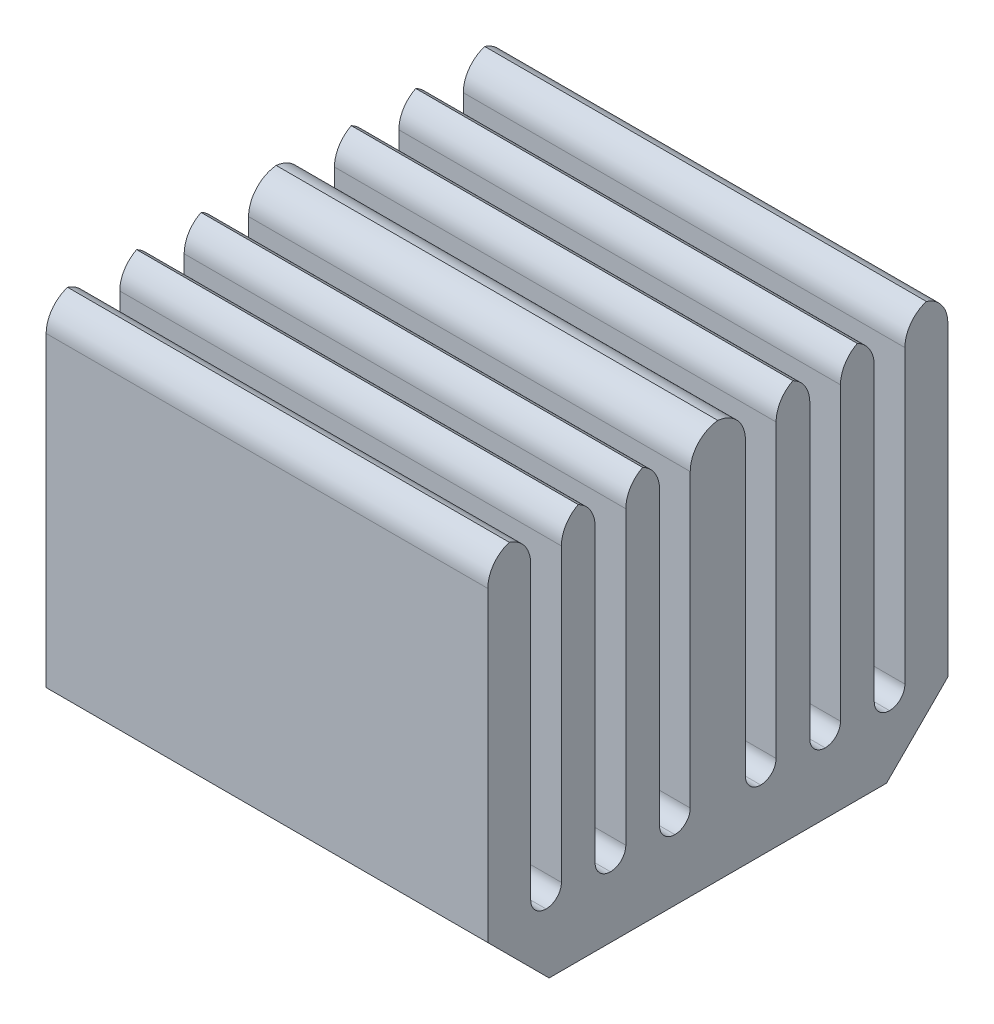
SolidWorks part; units mm, degrees
material "2.0060 (Cu-ETP)"
ref_plane "Ebene vorne" through (0, 0, 0) normal (0, 0, 1) x (1, 0, 0)
ref_plane "Ebene oben" through (0, 0, 0) normal (0, 1, 0) x (1, 0, 0)
ref_plane "Ebene rechts" through (0, 0, 0) normal (1, 0, 0) x (0, 0, -1)
sketch "Skizze1" plane through (0, 0, 0) normal (0, 1, 0) x (1, 0, 0)
  line L1 (-7.2, -7.5) -> (7.2, -7.5)
  line L2 (-7.2, -7.5) -> (-7.2, 7.5)
  line L3 (-7.2, 7.5) -> (7.2, 7.5)
  line L4 (7.2, -7.5) -> (7.2, 7.5)
  line L5 (-7.2, -7.5) -> (7.2, 7.5) construction
  line L6 (-7.2, 7.5) -> (7.2, -7.5) construction
  point P0 (0, 0)
  dimension "D1" = 14.4
  dimension "D2" = 15
extrude "Aufsatz-Linear austragen1" add sketch "Skizze1" along normal blind 13
sketch "Skizze2" plane through (0, 13, 0) normal (0, 1, 0) x (1, 0, 0)
  line L0 (-7.2, 7.5) -> (-7.2, -7.5) construction
  line L1 (-7.2, -6.1) -> (7.2, -6.1)
  line L2 (-7.2, -6.1) -> (-7.2, -5.1)
  line L3 (-7.2, -5.1) -> (7.2, -5.1)
  line L4 (7.2, -6.1) -> (7.2, -5.1)
  line L5 (7.2, -7.5) -> (7.2, 7.5) construction
  line L6 (7.2, 7.5) -> (-7.2, 7.5) construction
  line L7 (-7.2, -3) -> (7.2, -3)
  line L8 (-7.2, -3) -> (-7.2, -4)
  line L9 (-7.2, -4) -> (7.2, -4)
  line L10 (7.2, -3) -> (7.2, -4)
  line L11 (-7.2, -0.9) -> (7.2, -0.9)
  line L12 (-7.2, -0.9) -> (-7.2, -1.9)
  line L13 (-7.2, -1.9) -> (7.2, -1.9)
  line L14 (7.2, -0.9) -> (7.2, -1.9)
  line L15 (-7.2, 1.9) -> (7.2, 1.9)
  line L16 (-7.2, 1.9) -> (-7.2, 0.9)
  line L17 (-7.2, 0.9) -> (7.2, 0.9)
  line L18 (7.2, 1.9) -> (7.2, 0.9)
  line L19 (-7.2, 4) -> (7.2, 4)
  line L20 (-7.2, 4) -> (-7.2, 3)
  line L21 (-7.2, 3) -> (7.2, 3)
  line L22 (7.2, 4) -> (7.2, 3)
  line L23 (-7.2, 6.1) -> (7.2, 6.1)
  line L24 (-7.2, 6.1) -> (-7.2, 5.1)
  line L25 (-7.2, 5.1) -> (7.2, 5.1)
  line L26 (7.2, 6.1) -> (7.2, 5.1)
  line L27 (-7.2, -7.5) -> (7.2, -7.5) construction
  dimension "D1" = 1
  dimension "D2" = 1.4
  dimension "D3" = 1.1
  dimension "D4" = 1.1
  dimension "D5" = 1.1
  dimension "D6" = 1.1
  dimension "D7" = 1.4
extrude "Schnitt-Linear austragen1" cut sketch "Skizze2" against normal blind 11
fillet "Verrundung1" radius 1 14 edges at (0, 13, 7.5) (0, 13, 6.1) (0, 13, 5.1) (0, 13, 4) (0, 13, 3) (0, 13, 1.9) (0, 13, 0.9) (0, 13, -0.9) (0, 13, -1.9) (0, 13, -3) (0, 13, -4) (0, 13, -5.1) (0, 13, -6.1) (0, 13, -7.5)
chamfer "Fase1" distance 2 angle 45 2 edges at (0, 0, -7.5) (0, 0, 7.5)
fillet "Verrundung3" radius 0.5 12 edges at (0, 2, -5.1) (0, 2, -3) (0, 2, -0.9) (0, 2, 1.9) (0, 2, 4) (0, 2, 6.1) (0, 2, 5.1) (0, 2, 3) (0, 2, 0.9) (0, 2, -1.9) (0, 2, -4) (0, 2, -6.1)
